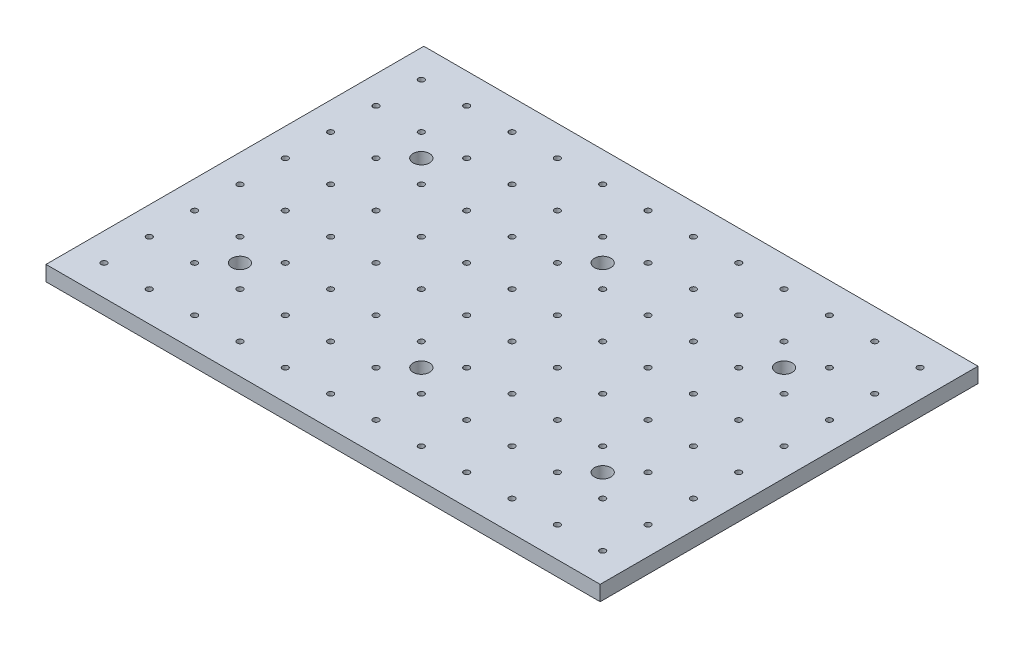
SolidWorks part; units mm, degrees
ref_plane "Front Plane" through (0, 0, 0) normal (0, 0, 1) x (1, 0, 0)
ref_plane "Top Plane" through (0, 0, 0) normal (0, 1, 0) x (1, 0, 0)
ref_plane "Right Plane" through (0, 0, 0) normal (1, 0, 0) x (0, 0, -1)
sketch "Sketch1" plane through (0, 0, 0) normal (0, 1, 0) x (1, 0, 0)
  line L1 (55, -37.5) -> (-55, -37.5)
  line L2 (55, -37.5) -> (55, 37.5)
  line L3 (55, 37.5) -> (-55, 37.5)
  line L4 (-55, -37.5) -> (-55, 37.5)
  line L5 (55, -37.5) -> (-55, 37.5) construction
  line L6 (55, 37.5) -> (-55, -37.5) construction
  point P0 (0, 0)
  dimension "D1" = 110
  dimension "D2" = 75
extrude "Boss-Extrude1" add sketch "Sketch1" along normal blind 3
sketch "Sketch2" plane through (0, 0, 0) normal (0, 1, 0) x (1, 0, 0)
  line L0 (0, -0.715) -> (0, 0.715) construction
  line L1 (-0.715, 0) -> (0.715, 0) construction
  circle A0 centre (-4.5, 4.5) radius 0.575
  dimension "D1" = 1.15
  dimension "D2" = 4.5
  dimension "D3" = 4.5
extrude "Cut-Extrude2" cut sketch "Sketch2" along normal through all
ref_axis "Axis1" through (-60.5, 0, 0) along (1, 0, 0)
ref_axis "Axis2" through (0, 0, 41.25) along (0, 0, -1)
pattern_linear "LPattern1" count 6 spacing 9 along (-1, 0, 0) count 4 spacing 9 along (0, 0, -1) of "Cut-Extrude2"
mirror "Mirror1" about plane through (0, 0, 0) normal (0, 0, 1) of "LPattern1", "Cut-Extrude2"
mirror "Mirror2" about plane through (0, 0, 0) normal (1, 0, 0) of "Cut-Extrude2", "Mirror1", "LPattern1"
hole_wizard "#4 Clearance Hole1" positions "Sketch3" profile "Sketch4" hole size "#4" standard "ANSI Inch" end condition through all
sketch "Sketch3" plane through (0, 3, 0) normal (0, 1, 0) x (1, 0, 0)
  line L1 (36, -18) -> (-36, -18) construction
  line L2 (36, -18) -> (36, 18) construction
  line L3 (36, 18) -> (-36, 18) construction
  line L4 (-36, -18) -> (-36, 18) construction
  line L5 (36, -18) -> (-36, 18) construction
  line L6 (36, 18) -> (-36, -18) construction
  line L7 (-1.65, 0) -> (1.65, 0) construction
  line L8 (0, -1.65) -> (0, 1.65) construction
  point P1 (-36, 18)
  point P136 (36, -18)
  point P137 (36, 18)
  point P138 (-36, -18)
  point P149 (0, 18)
  point P151 (0, -18)
  dimension "D1" = 18
  dimension "D2" = 36
sketch "Sketch4" plane through (-36, 3, -18) normal (1, 0, 0) x (0, 0, 1)
  line L0 (0, 0) -> (0, 3)
  line L1 (0, 3) -> (1.6319, 3)
  line L2 (1.6319, 3) -> (1.6319, 0)
  line L5 (1.6319, 0) -> (0, 0)
  line L11 (0, -6.35) -> (0, 107.95) construction
  dimension "Thru Hole Dia." = 3.2639
  dimension "Thru Hole Depth" = 3
